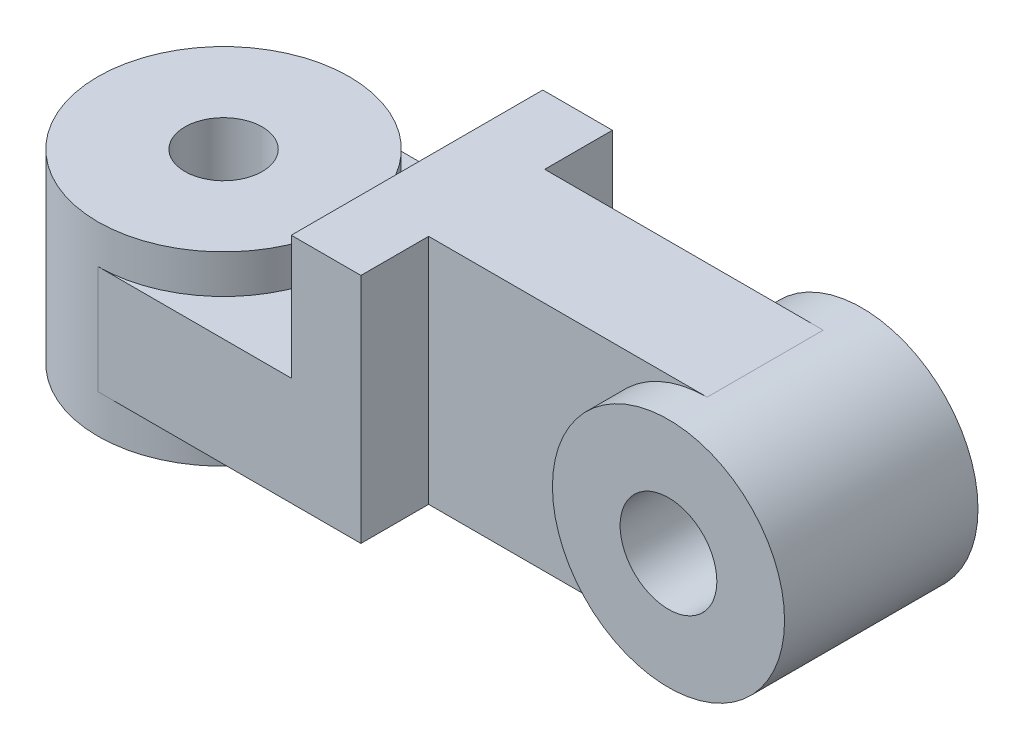
SolidWorks part; units mm, degrees
ref_plane "Front Plane" through (0, 0, 0) normal (0, 0, 1) x (1, 0, 0)
ref_plane "Top Plane" through (0, 0, 0) normal (0, 1, 0) x (1, 0, 0)
ref_plane "Right Plane" through (0, 0, 0) normal (1, 0, 0) x (0, 0, -1)
sketch "Sketch1" plane through (0, 0, 0) normal (0, 0, 1) x (1, 0, 0)
  line L0 (-68, 0) -> (-68, 28)
  line L1 (-68, 28) -> (-18, 28)
  line L2 (-18, 28) -> (-18, 60)
  line L3 (-18, 60) -> (0, 60)
  line L4 (0, 60) -> (0, 0)
  line L5 (0, 0) -> (-68, 0)
  line L6 (0, 60) -> (72, 60)
  line L7 (72, 60) -> (72, 0)
  line L8 (72, 0) -> (0, 0)
  dimension "D1" = 68
  dimension "D2" = 18
  dimension "D3" = 28
  dimension "D4" = 72
  dimension "D5" = 60
extrude "Boss-Extrude1" add sketch "Sketch1" along normal mid plane 65 contours L5 L4 L3 L2 L1 L0 region at (-28.1935, 20.9677, 0)
extrude "Boss-Extrude2" add sketch "Sketch1<3>" along normal mid plane 30 contours L8 L7 L6 L4 region at (36, 30, 0)
sketch "Sketch1<3>" plane through (0, 0, 0) normal (0, 0, 1) x (1, 0, 0) same geometry as "Sketch1"
sketch "Sketch2" plane through (0, 28, 0) normal (0, 1, 0) x (1, 0, 0)
  line L0 (-68, -32.5) -> (-68, 32.5) construction
  circle A0 centre (-68, 0) radius 32.5
extrude "Boss-Extrude3" add sketch "Sketch2" against normal blind 48 from offset 10 contours A0
sketch "Sketch3" plane through (0, 0, 15) normal (0, 0, 1) x (1, 0, 0)
  line L0 (72, 60) -> (72, 0) construction
  circle A0 centre (72, 30) radius 30
extrude "Boss-Extrude4" add sketch "Sketch3" against normal blind 50 from offset 10
sketch "Sketch4" plane through (0, 0, 25) normal (0, 0, 1) x (1, 0, 0)
  circle A0 centre (72, 30) radius 12.5
  dimension "D1" = 25
sketch "Sketch5" plane through (0, 38, 0) normal (0, 1, 0) x (1, 0, 0)
  circle A0 centre (-68, 0) radius 10
  dimension "D1" = 20
extrude "Cut-Extrude1" cut sketch "Sketch5" against normal through all
extrude "Cut-Extrude2" cut sketch "Sketch4" against normal through all both and the other way through all contours A0
